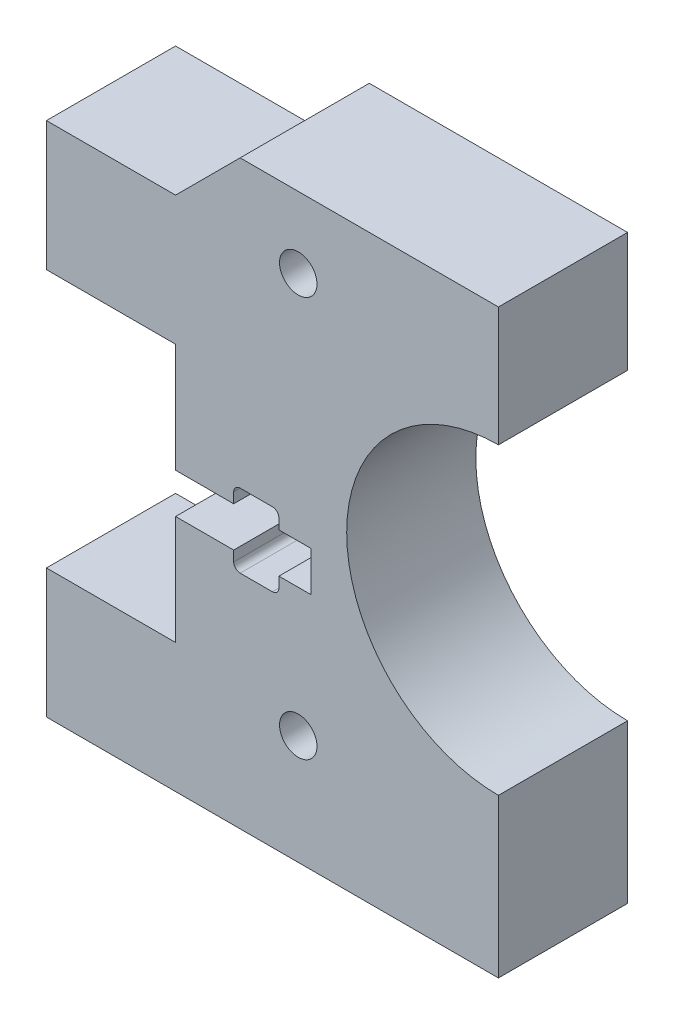
SolidWorks part; units mm, degrees
ref_plane "Front Plane" through (0, 0, 0) normal (0, 0, 1) x (1, 0, 0)
ref_plane "Top Plane" through (0, 0, 0) normal (0, 1, 0) x (1, 0, 0)
ref_plane "Right Plane" through (0, 0, 0) normal (1, 0, 0) x (0, 0, -1)
sketch "Sketch1" plane through (0, 0, 0) normal (0, 0, 1) x (1, 0, 0)
  line L0 (0, 0) -> (0, -50) construction
  line L1 (-10, -40) -> (0, -40) construction
  line L2 (25, -50) -> (25, 0) construction
  line L3 (25, 0) -> (0, 0) construction
  line L4 (0, 0) -> (0, -5)
  line L5 (0, -5) -> (-10, -5)
  line L6 (-10, -5) -> (-10, -15)
  line L7 (-10, -15) -> (0, -15)
  line L8 (0, -15) -> (0, -35)
  line L9 (25, -50) -> (0, -50) construction
  line L10 (0, -50) -> (25, -50)
  line L11 (-10, -35) -> (0, -35)
  line L12 (-10, -45) -> (-10, -35)
  line L13 (0, -45) -> (-10, -45)
  line L14 (25, -50) -> (25, 0)
  line L15 (0, 0) -> (25, 0)
  line L16 (0, -50) -> (0, -45)
  line L17 (-10, -10) -> (0, -10) construction
  line L18 (0, -25) -> (25, -25) construction
  dimension "D1" = 10
  dimension "D6" = 25
  dimension "D2" = 25
extrude "Boss-Extrude1" add sketch "Sketch1" along normal blind 10
sketch "Sketch2" plane through (0, 0, 10) normal (0, 0, 1) x (1, 0, 0)
  line L0 (25, -21) -> (0, -21) construction
  line L1 (25, -50) -> (25, 0) construction
  line L2 (0, -15) -> (0, -35) construction
  line L3 (25, -21) -> (9.5, -5.5) construction
  line L4 (25, -21) -> (9.5, -36.5) construction
  circle A0 centre (25, -21) radius 11.75
  circle A1 centre (9.5, -5.5) radius 1.45
  circle A2 centre (9.5, -36.5) radius 1.45
  point P6 (0, -25)
  dimension "D2" = 23.5
  dimension "D5" = 2.9
  dimension "D1" = 4
  dimension "D3" = 45
  dimension "D4" = 15.5
extrude "motor" cut sketch "Sketch2" against normal through all
sketch "Sketch3" plane through (0, 0, 10) normal (0, 0, 1) x (1, 0, 0)
  line L0 (0, -25) -> (10.5, -25) construction
  line L1 (0, -15) -> (0, -35) construction
  line L2 (10.5, -26.55) -> (10.5, -23.45) construction
  line L3 (10.5, -23.45) -> (0, -23.45) construction
  line L4 (0, -26.55) -> (0, -23.45)
  line L5 (0, -23.45) -> (4.5, -23.45)
  line L6 (4.5, -23.45) -> (4.5, -22.65)
  line L7 (5, -22.15) -> (7.5, -22.15)
  line L8 (8, -22.65) -> (8, -23.45)
  line L9 (8, -23.45) -> (10.5, -23.45)
  line L10 (10.5, -23.45) -> (10.5, -26.55)
  line L11 (10.5, -26.55) -> (0, -26.55) construction
  line L12 (8, -26.55) -> (10.5, -26.55)
  line L13 (8, -27.35) -> (8, -26.55)
  line L14 (5, -27.85) -> (7.5, -27.85)
  line L15 (4.5, -26.55) -> (4.5, -27.35)
  line L16 (0, -26.55) -> (4.5, -26.55)
  arc A0 (5, -27.85) -> (4.5, -27.35) centre (5, -27.35) cw
  arc A1 (8, -27.35) -> (7.5, -27.85) centre (7.5, -27.35) cw
  arc A2 (7.5, -22.15) -> (8, -22.65) centre (7.5, -22.65) cw
  arc A3 (4.5, -22.65) -> (5, -22.15) centre (5, -22.65) cw
  point P18 (4.5, -27.85)
  point P21 (8, -27.85)
  point P24 (8, -22.15)
  point P27 (4.5, -22.15)
  dimension "D6" = 0.5
  dimension "D1" = 1.55
  dimension "D2" = 8
  dimension "D3" = 10.5
  dimension "D4" = 2.85
  dimension "D5" = 3.5
extrude "screw" cut sketch "Sketch3" against normal through all
sketch "Sketch4" plane through (0, 0, 10) normal (0, 0, 1) x (1, 0, 0)
  line L0 (0, -45) -> (25, -45)
  line L1 (25, -50) -> (25, -32.75) construction
  line L2 (25, -45) -> (25, -50)
  line L3 (25, -50) -> (0, -50)
  line L4 (0, -50) -> (0, -45)
  line L5 (0, -5) -> (5, 0)
  line L6 (25, 0) -> (0, 0) construction
  line L7 (5, 0) -> (0, 0)
  line L8 (0, 0) -> (0, -5)
  dimension "D1" = 45
extrude "Cut-Extrude3" cut sketch "Sketch4" against normal through all
equation "\"X-ROD-SPACING\"=45"
equation "\"Y-ROD-SPACING\"=75"
equation "\"Z-ROD-SPACING\"=17.5"
equation "\"Y-BED-OFFSET\"=2"
equation "\"Y-BED-ROD-INSET\"=3.5"
equation "\"T-SLOT-NUT-FILLET-RADIUS\"=0.5"
equation "\"T-SLOT-SCREW-SHAFT-RADIUS\"=1.55"
equation "\"T-SLOT-SCREW-SHAFT-CUTOUT-LENGTH\"=11.0"
equation "\"T-SLOT-NUT-DEPTH\"=3.5"
equation "\"T-SLOT-NUT-WIDTH\"=2.85"
equation "\"T-SLOT-NUT-END-DISTANCE\"=8"
equation "\"ACRYLIC-THICKNESS\"=10"
equation "\"ACRYLIC-THICKNESS2\"=4.5"
equation "\"ACRYLIC-TAB-CUTOUT-SIZE\"=\"ACRYLIC-THICKNESS\"+\"ACRYLIC-TAB-TOLERANCE\"*2"
equation "\"ACRYLIC-TAB-WIDTH\"=\"ACRYLIC-THICKNESS\""
equation "\"ACRYLIC-M3-HOLE\"=2.9"
equation "\"SMOOTHROD-CAP-SCREW-DISTANCE\"=20"
equation "\"FRAME-WIDTH-INNER\"=370"
equation "\"NEMA17-HOLE-SPACING\"=31"
equation "\"NEMA17-CENTRAL-CUTOUT\"=22.5"
equation "\"Z-BRACKET-REACH\"=55"
equation "\"TOP-BRACKET-SPACING\"=40"
equation "\"SMOOTHROD-X-LENGTH\"=350"
equation "\"SMOOTHROD-Y-LENGTH\"=350"
equation "\"SMOOTHROD-Z-LENGTH\"=350"
equation "\"SMOOTHROD-TIGHTENING-HEADROOM\"=.25"
equation "\"LEADSCREW-Z-LENGTH\"=300"
equation "\"SCREW-LENGTH-FRAME\"=\"ACRYLIC-THICKNESS\" + 10"
equation "\"SCREW-HEAD-RADIUS\"=6"
equation "\"PRINTED-X-SMOOTHROD-DIAMETER\"=9.0"
equation "\"PRINTED-X-SMOOTHROD-CUTOUT\"=10"
equation "\"PRINTED-X-BASE-HEIGHT\"=10"
equation "\"PRINTED-LM8UU-CUTOUT-SIZE\"=15.5"
equation "\"PRINTED-LM8UU-CUTOUT-LENGTH\"=24.5"
equation "\"PRINTED-X-IDLER-HEIGHT\"=16"
equation "\"PSU-MOUNTING-WIDTH\"=95"
equation "\"PSU-MOUNTING-HEIGHT\"=177"
equation "\"D1@Sketch1\"=10"
equation "\"D3@Sketch1\"=10"
equation "\"D1@Boss-Extrude1\"=\"ACRYLIC-THICKNESS\""
equation "\"D2@Sketch2\"=\"NEMA17-CENTRAL-CUTOUT\"+1"
equation "\"D4@Sketch2\"=\"NEMA17-HOLE-SPACING\"/2"
equation "\"D5@Sketch2\"=\"ACRYLIC-M3-HOLE\""
equation "\"D1@Sketch3\"=\"T-SLOT-SCREW-SHAFT-RADIUS\""
equation "\"D4@Sketch3\"=\"T-SLOT-NUT-WIDTH\""
equation "\"D2@Sketch3\"=\"T-SLOT-NUT-END-DISTANCE\""
equation "\"D5@Sketch3\"=\"T-SLOT-NUT-DEPTH\""
equation "\"D6@Sketch3\"=\"T-SLOT-NUT-FILLET-RADIUS\""
